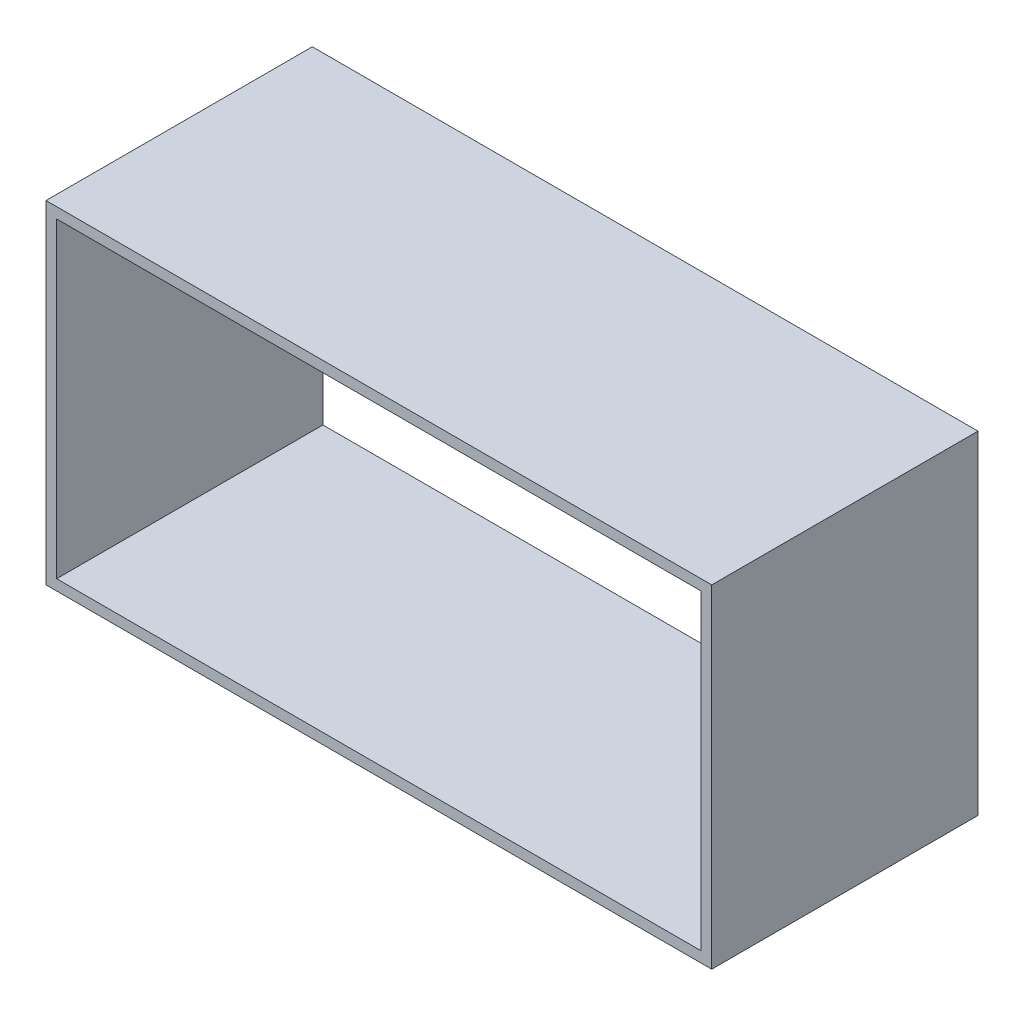
SolidWorks part; units mm, degrees
ref_plane "Ebene vorne" through (0, 0, 0) normal (0, 0, 1) x (1, 0, 0)
ref_plane "Ebene oben" through (0, 0, 0) normal (0, 1, 0) x (1, 0, 0)
ref_plane "Ebene rechts" through (0, 0, 0) normal (1, 0, 0) x (0, 0, -1)
sketch "Skizze1" plane through (0, 0, 0) normal (0, 0, 1) x (1, 0, 0)
  line L1 (0, 125) -> (250, 125)
  line L2 (0, 125) -> (0, 0)
  line L3 (0, 0) -> (250, 0)
  line L4 (250, 125) -> (250, 0)
  line L5 (246, 121) -> (4, 121)
  line L6 (246, 121) -> (246, 4)
  line L7 (246, 4) -> (4, 4)
  line L8 (4, 121) -> (4, 4)
  point P4 (0, 0)
  dimension "D1" = 250
  dimension "D2" = 125
  dimension "D3" = 4
  dimension "D4" = 4
  dimension "D5" = 4
  dimension "D6" = 4
extrude "Aufsatz-Linear austragen1" add sketch "Skizze1" along normal blind 100
